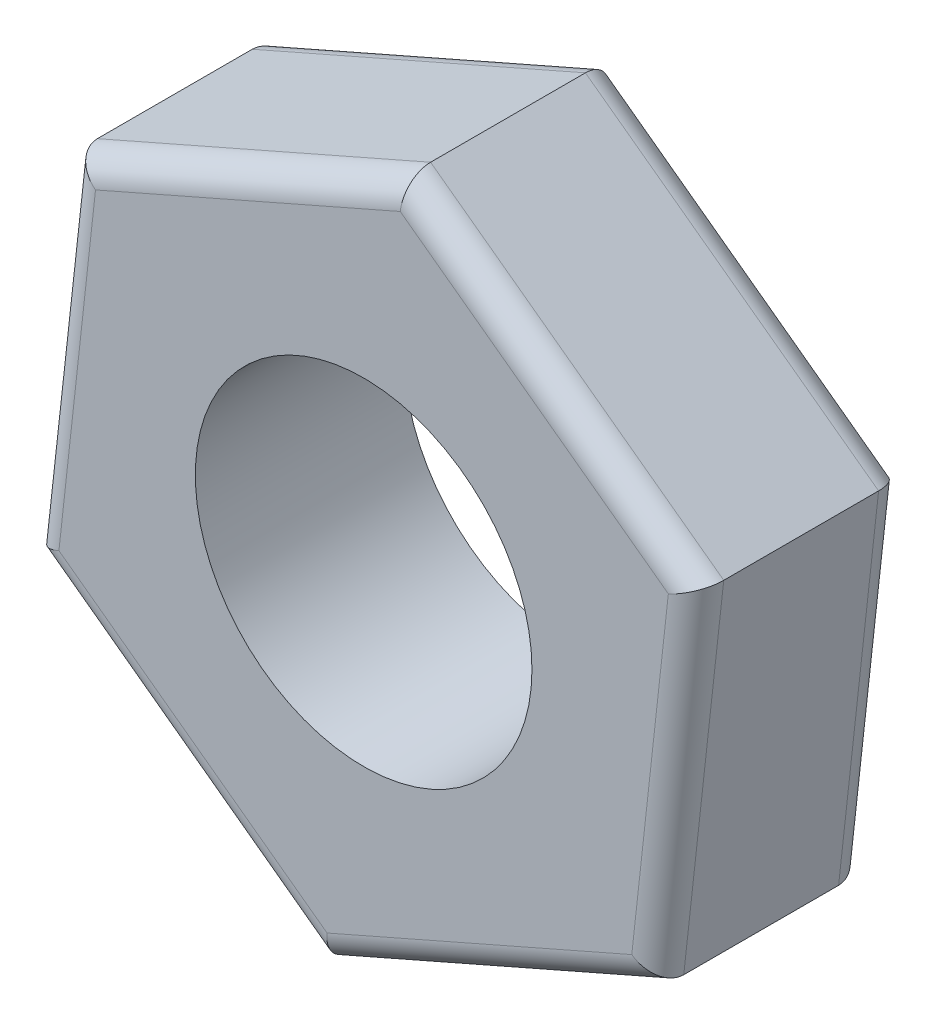
SolidWorks part; units mm, degrees
ref_plane "Front Plane" through (0, 0, 0) normal (0, 0, 1) x (1, 0, 0)
ref_plane "Top Plane" through (0, 0, 0) normal (0, 1, 0) x (1, 0, 0)
ref_plane "Right Plane" through (0, 0, 0) normal (1, 0, 0) x (0, 0, -1)
sketch "Sketch1" plane through (0, 0, 0) normal (0, 0, 1) x (1, 0, 0)
  line L1 (0.2971, 2.6856) -> (-2.1772, 1.6001)
  line L2 (-2.1772, 1.6001) -> (-2.4744, -1.0855)
  line L3 (-2.4744, -1.0855) -> (-0.2971, -2.6856)
  line L4 (-0.2971, -2.6856) -> (2.1772, -1.6001)
  line L5 (2.1772, -1.6001) -> (2.4744, 1.0855)
  line L6 (2.4744, 1.0855) -> (0.2971, 2.6856)
  circle A0 centre (0, 0) radius 2.34 construction
  dimension "D1" = 4.68
extrude "Boss-Extrude1" add sketch "Sketch1" along normal blind 1.55
fillet "Fillet1" radius 0.2 12 edges at (-2.3258, 0.2573, 0) (0.9401, -2.1429, 0) (2.3258, -0.2573, 0) (1.3858, 1.8855, 0) (-0.9401, 2.1429, 0) (-1.3858, -1.8855, 0) (-1.3858, -1.8855, 1.55) (-2.3258, 0.2573, 1.55) (0.9401, -2.1429, 1.55) (2.3258, -0.2573, 1.55) (1.3858, 1.8855, 1.55) (-0.9401, 2.1429, 1.55)
hole_wizard "Ø2.5mm Dowel Hole1" positions "Sketch2" profile "Sketch4" hole size "Ø2.5" standard "ANSI Metric" end condition through all
sketch "Sketch2" plane through (0, 0, 1.55) normal (0, 0, 1) x (1, 0, 0)
  point P0 (0, 0)
sketch "Sketch4" plane through (0, 0, 1.55) normal (1, 0, 0) x (0, -1, 0)
  line L0 (0, 0) -> (0, 1.55)
  line L1 (0, 1.55) -> (1.25, 1.55)
  line L2 (1.25, 1.55) -> (1.25, 0)
  line L5 (1.25, 0) -> (0, 0)
  line L11 (0, -6.35) -> (0, 107.95) construction
  dimension "Thru Hole Dia." = 2.5
  dimension "Thru Hole Depth" = 1.55
